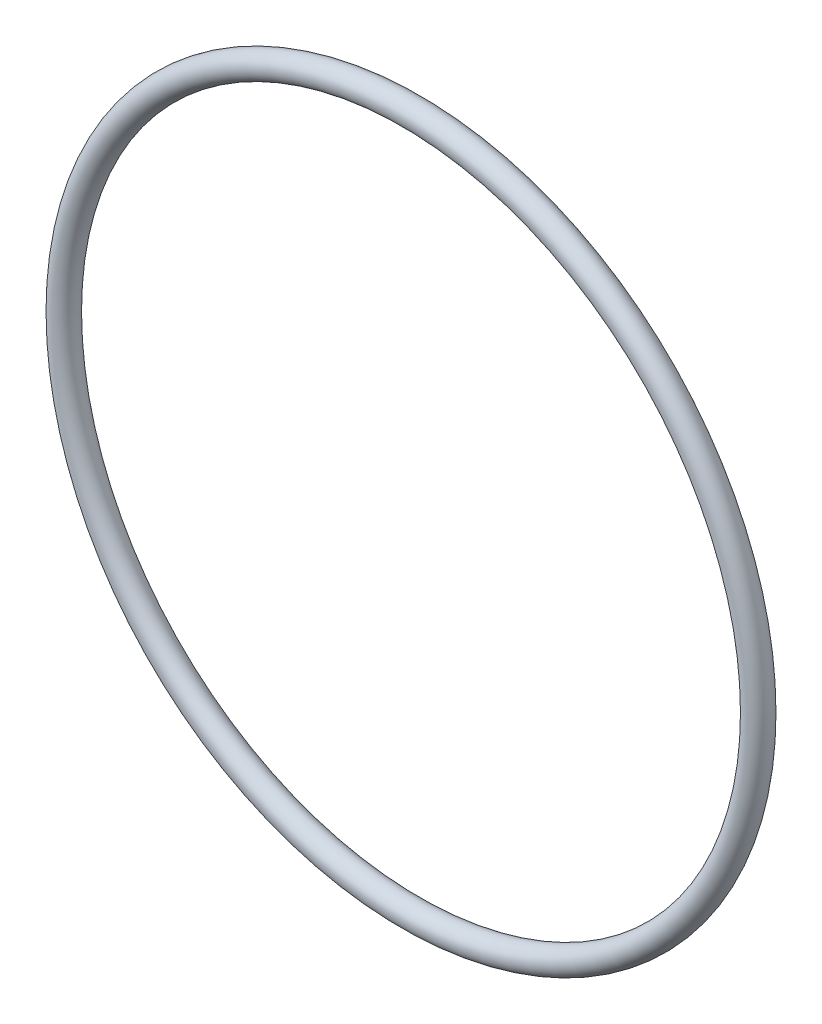
SolidWorks part; units mm, degrees
material "Rubber"
ref_plane "Front" through (0, 0, 0) normal (0, 0, 1) x (1, 0, 0)
ref_plane "Top" through (0, 0, 0) normal (0, 1, 0) x (1, 0, 0)
ref_plane "Right" through (0, 0, 0) normal (1, 0, 0) x (0, 0, -1)
sketch "Sketch1" plane through (0, 0, 0) normal (1, 0, 0) x (0, -1, 0)
  line L0 (0, -0.889) -> (0, 0.889) construction
  line L2 (-27.9959, 0) -> (27.9959, 0) construction
  line L3 (-23.6728, 0) -> (23.6728, 0) construction
  circle A0 centre (24.5618, 0) radius 0.889
  point P9 (23.6728, 0)
  point P10 (25.4508, 0)
  point P13 (24.5618, 0.889)
  point P14 (24.5618, -0.889)
  dimension "Width" = 1.778
  dimension "ID" = 47.3456
revolve "Revolve1" add sketch "Sketch1" angle 360 about L0
